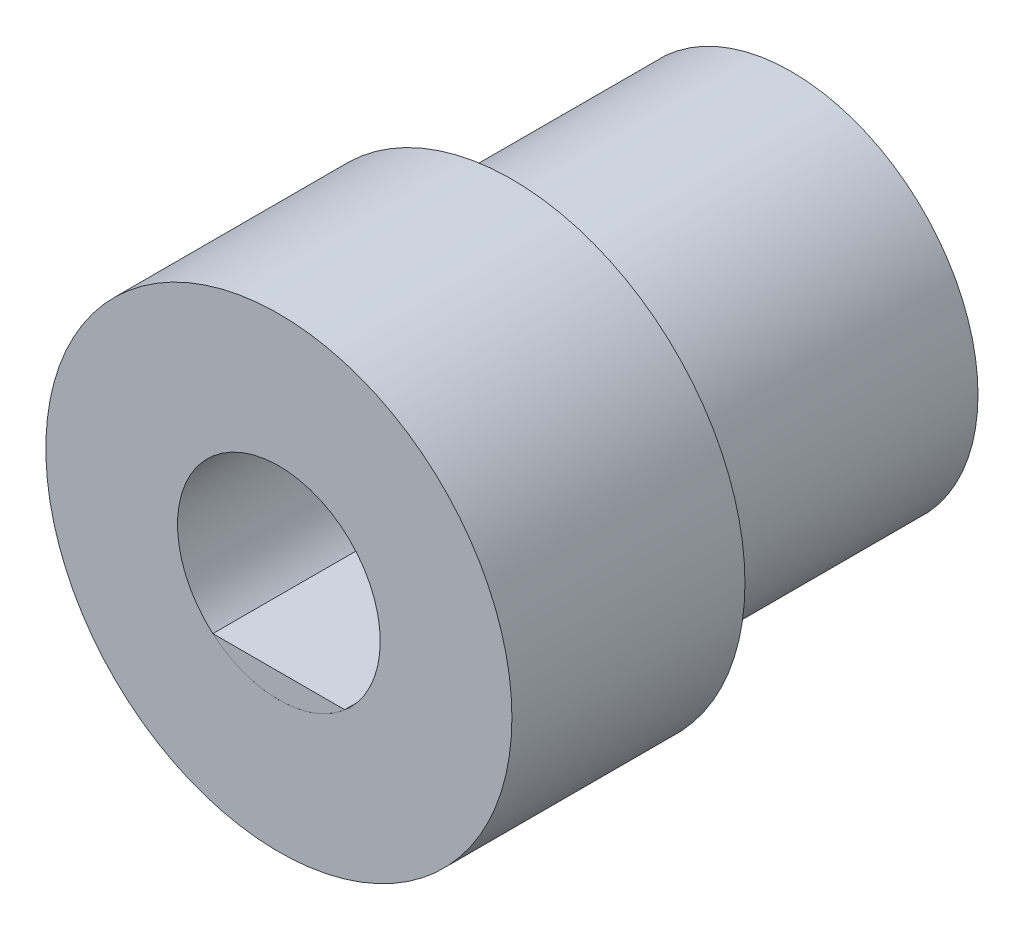
SolidWorks part; units mm, degrees
ref_plane "Plan de face" through (0, 0, 0) normal (0, 0, 1) x (1, 0, 0)
ref_plane "Plan de dessus" through (0, 0, 0) normal (0, 1, 0) x (1, 0, 0)
ref_plane "Plan de droite" through (0, 0, 0) normal (1, 0, 0) x (0, 0, -1)
sketch "Esquisse1" plane through (0, 0, 0) normal (0, 0, 1) x (1, 0, 0)
  circle A0 centre (0, 0) radius 10
  dimension "D1" = 20
extrude "Boss.-Extru.1" add sketch "Esquisse1" along normal blind 10
sketch "Esquisse2" plane through (0, 0, 0) normal (0, 0, -1) x (-1, 0, 0)
  circle A0 centre (0, 0) radius 8
  dimension "D1" = 16
extrude "Boss.-Extru.2" add sketch "Esquisse2" along normal blind 12 separate body
sketch "Esquisse3" plane through (0, 0, 10) normal (0, 0, 1) x (1, 0, 0)
  circle A0 centre (0, 0) radius 4.35
  dimension "D1" = 8.7
extrude "Enlèv. mat.-Extru.1" cut sketch "Esquisse3" against normal up to next (10 mm away)
sketch "Esquisse4" plane through (0, 0, -12) normal (0, 0, -1) x (-1, 0, 0)
  circle A0 centre (0, 0) radius 2.35
  dimension "D1" = 4.7
extrude "Enlèv. mat.-Extru.2" cut sketch "Esquisse4" against normal up to next (12 mm away)
sketch "Esquisse5" plane through (0, 0, 10) normal (0, 0, 1) x (1, 0, 0)
  line L0 (-2.8342, -3.3) -> (2.8342, -3.3)
  arc A0 (-2.8342, -3.3) -> (2.8342, -3.3) centre (0, 0) ccw
  circle A1 centre (0, 0) radius 4.35 construction
  dimension "D1" = 3.3
extrude "Boss.-Extru.3" add sketch "Esquisse5" against normal up to next separate body
sketch "Esquisse6" plane through (0, 0, -12) normal (0, 0, -1) x (-1, 0, 0)
  line L0 (-2.0205, -1.2) -> (2.0205, -1.2)
  arc A0 (2.0205, -1.2) -> (-2.0205, -1.2) centre (0, 0) cw
  circle A1 centre (0, 0) radius 2.35 construction
  dimension "D1" = 1.2
extrude "Boss.-Extru.4" add sketch "Esquisse6" against normal up to surface (12 mm away) up to face at (4.35, 0, 0)
